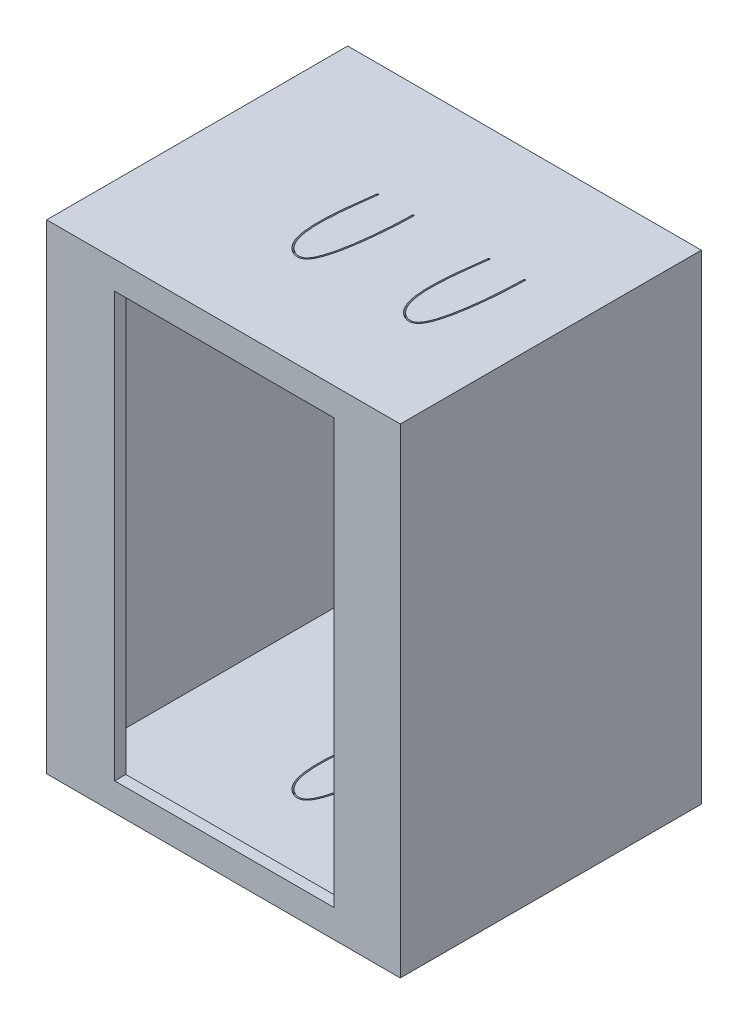
SolidWorks part; units mm, degrees
ref_plane "Front Plane" through (0, 0, 0) normal (0, 0, 1) x (1, 0, 0)
ref_plane "Top Plane" through (0, 0, 0) normal (0, 1, 0) x (1, 0, 0)
ref_plane "Right Plane" through (0, 0, 0) normal (1, 0, 0) x (0, 0, -1)
sketch "Sketch1" plane through (0, 0, 0) normal (0, 0, 1) x (1, 0, 0)
  line L0 (-14.745, 28.505) -> (-14.745, -28.505)
  line L1 (-13.745, 27.505) -> (13.745, 27.505) construction
  line L2 (-13.745, 27.505) -> (-13.745, -27.505) construction
  line L3 (-13.745, -27.505) -> (13.745, -27.505) construction
  line L4 (13.745, 27.505) -> (13.745, -27.505) construction
  line L5 (-14.745, -28.505) -> (14.745, -28.505)
  line L6 (14.745, 28.505) -> (14.745, -28.505)
  line L7 (-14.745, 28.505) -> (14.745, 28.505)
  line L12 (-21.8901, -18.3554) -> (-21.8901, -12.9446) construction
  line L13 (-22.3901, 30.745) -> (22.15, 30.745)
  line L14 (-22.3901, 30.745) -> (-22.3901, -30.755)
  line L15 (-22.3901, -30.755) -> (22.15, -30.755)
  line L16 (22.15, 30.745) -> (22.15, -30.755)
  line L17 (21.175, 30.245) -> (-15.825, 30.245) construction
  line L18 (21.175, -30.255) -> (-15.825, -30.255) construction
  line L19 (21.65, 17.5) -> (21.65, 18.5) construction
  line L20 (-23.8901, 32.245) -> (23.65, 32.245)
  line L21 (23.65, 32.245) -> (23.65, -32.255)
  line L22 (-23.8901, -32.255) -> (23.65, -32.255)
  line L23 (-23.8901, 32.245) -> (-23.8901, -32.255)
  dimension "D3" = 0.5
  dimension "D4" = 0.5
  dimension "D5" = 0.5
  dimension "D6" = 0.5
  dimension "D1" = 1
  dimension "D7" = 1.5
extrude "Boss-Extrude1" add sketch "Sketch1" along normal blind 1.5 contours L16 L13 L14 L15 L0 L7 L6 L5 | L20 L23 L22 L21 L13 L16 L15 L14 region at (-0.1201, 29.9857, 0) region at (-0.1201, 31.4437, 0)
extrude "Boss-Extrude2" add sketch "Sketch1<3>" against normal offset from surface (37.4706 mm away) 1 contours L20 L23 L22 L21 L13 L16 L15 L14 region at (-0.1201, 31.4437, 0) offset beyond the face yes
sketch "Sketch1<3>" plane through (0, 0, 0) normal (0, 0, 1) x (1, 0, 0) same geometry as "Sketch1"
extrude "Boss-Extrude3" add sketch "Sketch1<4>" against normal blind 1.5 from surface contours L22 L21 L20 L23 starting at face at (-0.1201, -0.005, -37.4706)
sketch "Sketch1<4>" plane through (0, 0, 0) normal (0, 0, 1) x (1, 0, 0) same geometry as "Sketch1"
sketch "Sketch2" plane through (-23.8901, 0, 0) normal (-1, 0, 0) x (0, 0, 1)
  line L1 (-11.5598, -11.7638) -> (-25.7485, -11.7638)
  line L2 (-11.5598, -11.7638) -> (-11.5598, -19.6113)
  line L3 (-11.5598, -19.6113) -> (-25.7485, -19.6113)
  line L4 (-25.7485, -11.7638) -> (-25.7485, -19.6113)
  circle A0 centre (-21.3, 10.4) radius 10.1345
extrude "Cut-Extrude1" cut sketch "Sketch2" against normal blind 0.5
ref_plane "Plane1" through (22.15, 30.745, 0) normal (0, 0, 1) x (1, 0, 0)
sketch "Sketch5" plane through (0, 32.245, 0) normal (0, 1, 0) x (1, 0, 0)
  arc A0 (-4.5048, 23.6662) -> (-4.7029, 23.6931) centre (-4.6039, 23.6796) ccw
  arc A1 (0.1358, 23.6254) -> (0.3358, 23.6236) centre (0.2358, 23.6245) cw
  arc A2 (15.1358, 23.6254) -> (15.3358, 23.6236) centre (15.2358, 23.6245) cw
  arc A3 (10.4952, 23.6662) -> (10.2971, 23.6931) centre (10.3961, 23.6796) ccw
  spline S0 degree 3 poles (-4.5048, 23.6662) (-5.2392, 18.256) (-5.9743, 11.9012) (-0.4973, 10.6022) (0.1125, 21.0571) (0.1358, 23.6254) knots 0 0 0 0 0.524282 0.624282 1 1 1 1
  spline S1 degree 1 poles (-4.7029, 23.6931) (0.3358, 23.6236) knots 0 0 1 1 construction
  spline S2 degree 3 poles (-4.7029, 23.6931) (-4.7901, 23.051) (-4.9627, 21.7572) (-5.2553, 19.2379) (-5.4536, 16.2874) (-5.2363, 13.86) (-4.6793, 12.3637) (-4.0254, 11.5156) (-3.2428, 11.0529) (-2.4983, 11.0026) (-1.7571, 11.3381) (-1.1071, 12.4625) (-0.5274, 14.5375) (-0.1173, 17.0538) (0.1061, 19.2273) (0.2247, 20.8404) (0.2864, 21.9455) (0.3174, 22.738) (0.3313, 23.2853) (0.3348, 23.5064) (0.3358, 23.6236) knots 0 0 0 0 0.0625 0.125 0.25 0.375 0.4375 0.5 0.5625 0.59375 0.625 0.6875 0.75 0.8125 0.875 0.90625 0.9375 0.96875 0.984375 1 1 1 1
  spline S3 degree 3 poles (10.4952, 23.6662) (9.7608, 18.256) (9.0257, 11.9012) (14.5027, 10.6022) (15.1125, 21.0571) (15.1358, 23.6254) knots 0 0 0 0 0.524282 0.624282 1 1 1 1
  spline S4 degree 3 poles (10.2971, 23.6931) (10.2099, 23.051) (10.0373, 21.7572) (9.7447, 19.2379) (9.5464, 16.2874) (9.7637, 13.86) (10.3207, 12.3637) (10.9746, 11.5156) (11.7572, 11.0529) (12.5017, 11.0026) (13.2429, 11.3381) (13.8929, 12.4625) (14.4726, 14.5375) (14.8827, 17.0538) (15.1061, 19.2273) (15.2247, 20.8404) (15.2864, 21.9455) (15.3174, 22.738) (15.3313, 23.2853) (15.3348, 23.5064) (15.3358, 23.6236) knots 0 0 0 0 0.0625 0.125 0.25 0.375 0.4375 0.5 0.5625 0.59375 0.625 0.6875 0.75 0.8125 0.875 0.90625 0.9375 0.96875 0.984375 1 1 1 1
  dimension "D1" = 0.2
  dimension "D2" = 2
extrude "Cut-Extrude2" cut sketch "Sketch5" against normal through all
